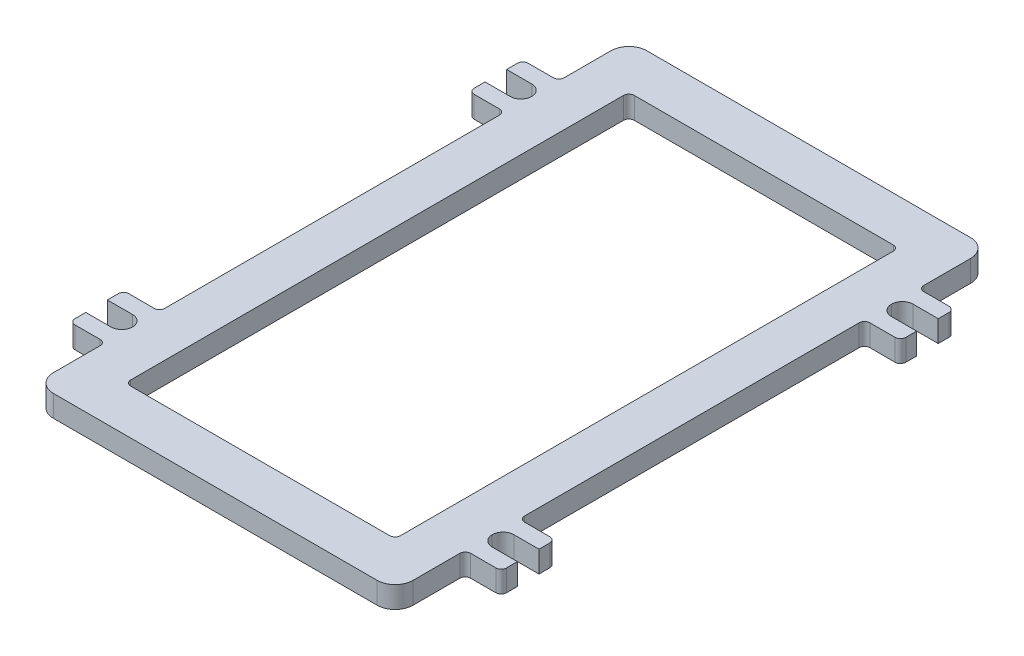
SolidWorks part; units mm, degrees
other "Markup1"
sketch "Sketch1" plane through (0, 0, 0) normal (0.4, 0.515, 0.7581) x (0.8844, 0, -0.4667)
ref_plane "Front Plane" through (0, 0, 0) normal (0, 0, 1) x (1, 0, 0)
ref_plane "Top Plane" through (0, 0, 0) normal (0, 1, 0) x (1, 0, 0)
ref_plane "Right Plane" through (0, 0, 0) normal (1, 0, 0) x (0, 0, -1)
sketch "Sketch2" plane through (0, 0, 0) normal (0, 1, 0) x (1, 0, 0)
  line L0 (-269.8153, 0) -> (252.106, 0) construction
  line L1 (-90, -165) -> (90, -165)
  line L2 (-100, -155) -> (-100, 155)
  line L3 (-90, 165) -> (90, 165)
  line L4 (100, -155) -> (100, 155)
  line L5 (-72, -140) -> (72, -140)
  line L6 (-75, -137) -> (-75, 137)
  line L7 (-72, 140) -> (72, 140)
  line L8 (75, -137) -> (75, 137)
  line L9 (0, 0) -> (0, 119.448) construction
  arc A0 (-72, -140) -> (-75, -137) centre (-72, -137) cw
  arc A1 (72, -140) -> (75, -137) centre (72, -137) ccw
  arc A2 (72, 140) -> (75, 137) centre (72, 137) cw
  arc A3 (-75, 137) -> (-72, 140) centre (-72, 137) cw
  arc A4 (90, -165) -> (100, -155) centre (90, -155) ccw
  arc A5 (-90, -165) -> (-100, -155) centre (-90, -155) cw
  arc A6 (90, 165) -> (100, 155) centre (90, 155) cw
  arc A7 (-100, 155) -> (-90, 165) centre (-90, 155) cw
  point P21 (-100, -165)
  dimension "D7" = 3
  dimension "D8" = 10
  dimension "D1" = 200
  dimension "D2" = 25
  dimension "D3" = 25
  dimension "D4" = 25
  dimension "D5" = 330
  dimension "D6" = 25
extrude "Boss-Extrude1" add sketch "Sketch2" along normal blind 12
sketch "Sketch3" plane through (0, 0, 0) normal (0, 1, 0) x (1, 0, 0)
  line L0 (75, 126) -> (120, 126)
  line L1 (120, 126) -> (120, 117)
  line L2 (120, 117) -> (97, 117)
  line L3 (97, 117) -> (97, 105)
  line L4 (97, 105) -> (120, 105)
  line L5 (120, 105) -> (120, 96)
  line L6 (120, 96) -> (75, 96)
  line L7 (75, 96) -> (75, 126)
  line L8 (229.6415, 111) -> (153.4507, 111) construction
  line L9 (90, 165) -> (-90, 165) construction
  line L10 (0, 365.9318) -> (0, -49.5323) construction
  line L11 (75, -137) -> (75, 137) construction
  line L12 (-75, 137) -> (-75, -137) construction
  line L13 (100, -155) -> (100, 155) construction
  dimension "D1" = 54
  dimension "D2" = 20
  dimension "D3" = 3
  dimension "D4" = 12
  dimension "D5" = 30
extrude "Boss-Extrude2" add sketch "Sketch3" along normal blind 12
mirror "Mirror3" about plane through (0, 0, 0) normal (1, 0, 0) of "Boss-Extrude2"
mirror "Mirror4" about plane through (0, 0, 0) normal (0, 0, 1) of "Mirror3", "Boss-Extrude2"
fillet "Fillet3" radius 6 8 edges at (-100, 6, 117) (-100, 6, 105) (100, 6, 117) (100, 6, 105) (100, 6, -105) (100, 6, -117) (-100, 6, -105) (-100, 6, -117)
fillet "Fillet4" radius 3 16 edges at (-100, 6, -96) (-120, 6, -96) (-100, 6, -126) (-120, 6, -126) (100, 6, -126) (120, 6, -126) (100, 6, -96) (120, 6, -96) (100, 6, 126) (120, 6, 126) (120, 6, 96) (100, 6, 96) (-120, 6, 126) (-100, 6, 126) (-120, 6, 96) (-100, 6, 96)
